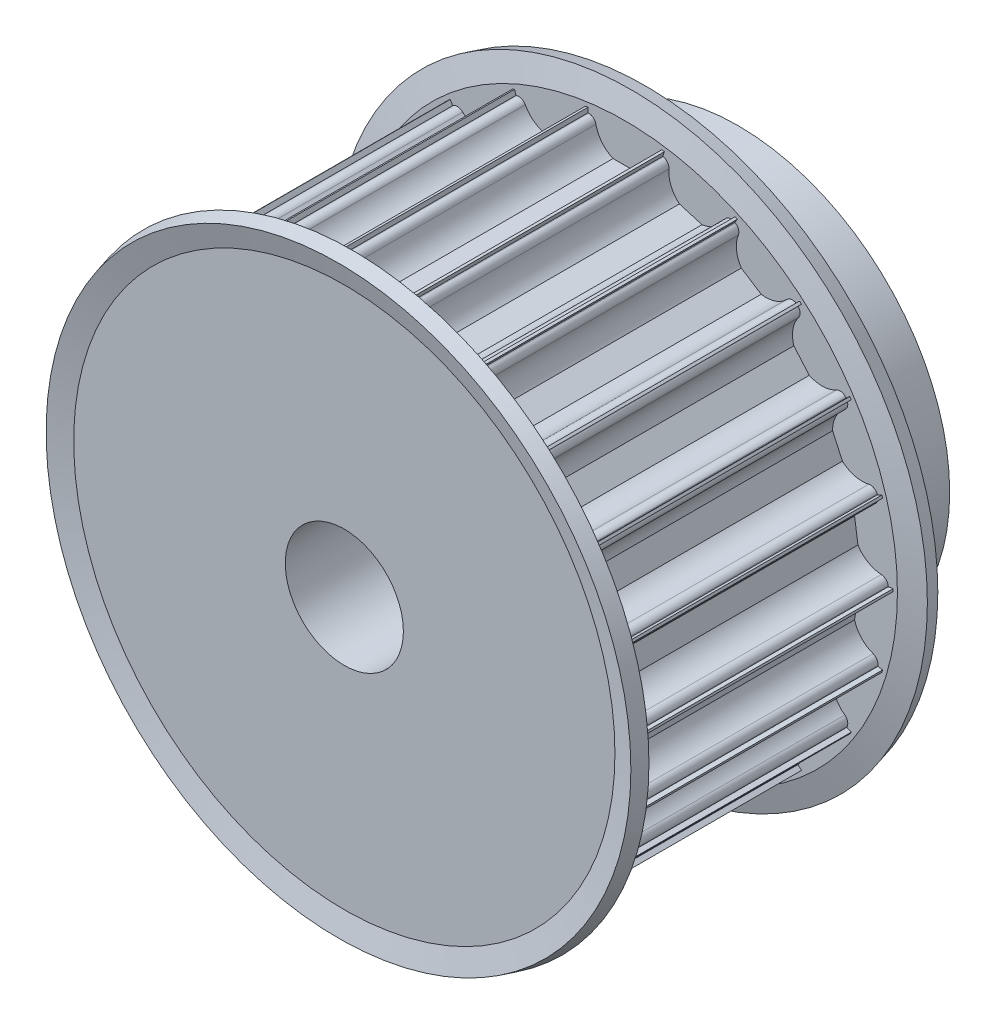
SolidWorks part; units mm, degrees
ref_plane "Front Plane" through (0, 0, 0) normal (0, 0, 1) x (1, 0, 0)
ref_plane "Top Plane" through (0, 0, 0) normal (0, 1, 0) x (1, 0, 0)
ref_plane "Right Plane" through (0, 0, 0) normal (1, 0, 0) x (0, 0, -1)
ref_axis "Axis1" through (0, 0, 101.7273) along (0, 0, -1)
sketch "Sketch1" plane through (0, 0, 0) normal (1, 0, 0) x (0, 0, -1)
  line L0 (0, 6) -> (0, 27.25)
  line L1 (0, 27.25) -> (30, 27.25)
  line L2 (30, 27.25) -> (30, 21.5)
  line L3 (30, 21.5) -> (40, 21.5)
  line L4 (40, 21.5) -> (40, 6)
  line L5 (40, 6) -> (0, 6)
  line L6 (-101.7273, 0) -> (118.6558, 0) construction
  dimension "D1" = 6
  dimension "D2" = 21.25
  dimension "D3" = 30
  dimension "D4" = 10
  dimension "D5" = 15.5
revolve "Revolve1" add sketch "Sketch1" angle 360 about axis through (0, 0, 101.7273) along (0, 0, -1)
sketch "Sketch2" plane through (0, 0, 0) normal (0, 0, 1) x (1, 0, 0)
  line L0 (3.6742, 26.5) -> (3.75, 26.5)
  line L9 (-3.75, 26.5) -> (-3.6742, 26.5)
  line L10 (-3.75, 26.5) -> (-3.75, 28.5)
  line L11 (-3.75, 28.5) -> (3.75, 28.5)
  line L12 (3.75, 26.5) -> (3.75, 28.5)
  line L13 (-1.199, 23.75) -> (1.199, 23.75)
  arc A0 (-2.9394, 25.9) -> (-1.199, 23.75) centre (0, 26.5) ccw
  arc A1 (-2.9394, 25.9) -> (-3.6742, 26.5) centre (-3.6742, 25.75) ccw
  arc A2 (3.6742, 26.5) -> (2.9394, 25.9) centre (3.6742, 25.75) ccw
  arc A3 (1.199, 23.75) -> (2.9394, 25.9) centre (0, 26.5) ccw
  dimension "D1" = 2
  dimension "D2" = 7.5
  dimension "D3" = 3
  dimension "D5" = 0.75
  dimension "D6" = 0.75
  dimension "D4" = 26.5
  dimension "D7" = 2.75
extrude "Cut-Extrude1" cut sketch "Sketch2" against normal through all
pattern_circular "CirPattern1" count 22 over 360 about axis through (0, 0, 101.7273) along (0, 0, -1) of "Cut-Extrude1"
sketch "Sketch3" plane through (0, 0, 0) normal (1, 0, 0) x (0, 0, -1)
  line L0 (1.5, 27.6907) -> (0.0511, 27.3025) construction
  line L1 (0, 27.6907) -> (1.5, 27.6907) construction
  line L2 (0, 27.6907) -> (0, 22.6907)
  line L3 (0, 22.6907) -> (1.5, 22.6907)
  line L4 (1.5, 27.6907) -> (1.5, 22.6907)
  line L5 (1.5, 27.6907) -> (0.8569, 30.0907)
  line L6 (0.0511, 27.3025) -> (-0.592, 29.7025)
  line L7 (0.8569, 30.0907) -> (-0.592, 29.7025)
  line L8 (0, 25.679) -> (0, 23.1257) construction
  line L9 (30, 26.9907) -> (0, 26.9907) construction
  line L10 (15, 36.1946) -> (15, -38.4551) construction
  line L11 (30, 27.6907) -> (28.5, 27.6907) construction
  line L12 (29.1431, 30.0907) -> (30.592, 29.7025)
  line L13 (29.9489, 27.3025) -> (30.592, 29.7025)
  line L14 (28.5, 27.6907) -> (29.1431, 30.0907)
  line L15 (28.5, 27.6907) -> (28.5, 22.6907)
  line L16 (30, 22.6907) -> (28.5, 22.6907)
  line L17 (30, 27.6907) -> (30, 22.6907)
  line L18 (28.5, 27.6907) -> (29.9489, 27.3025) construction
  dimension "D1" = 1.5
  dimension "D2" = 5
  dimension "D3" = 1.5
  dimension "D4" = 2.4
  dimension "D5" = 165
  dimension "D6" = 0.7
revolve "Revolve2" add sketch "Sketch3" angle 360 about axis through (0, 0, 101.7273) along (0, 0, -1) region at (0, 26.3219, -0.6556)
revolve "Revolve3" add sketch "Sketch3<4>" angle 360 about axis through (0, 0, 101.7273) along (0, 0, -1) region at (0, 26.3219, -29.3444)
sketch "Sketch3<4>" plane through (0, 0, 0) normal (1, 0, 0) x (0, 0, -1) same geometry as "Sketch3"
